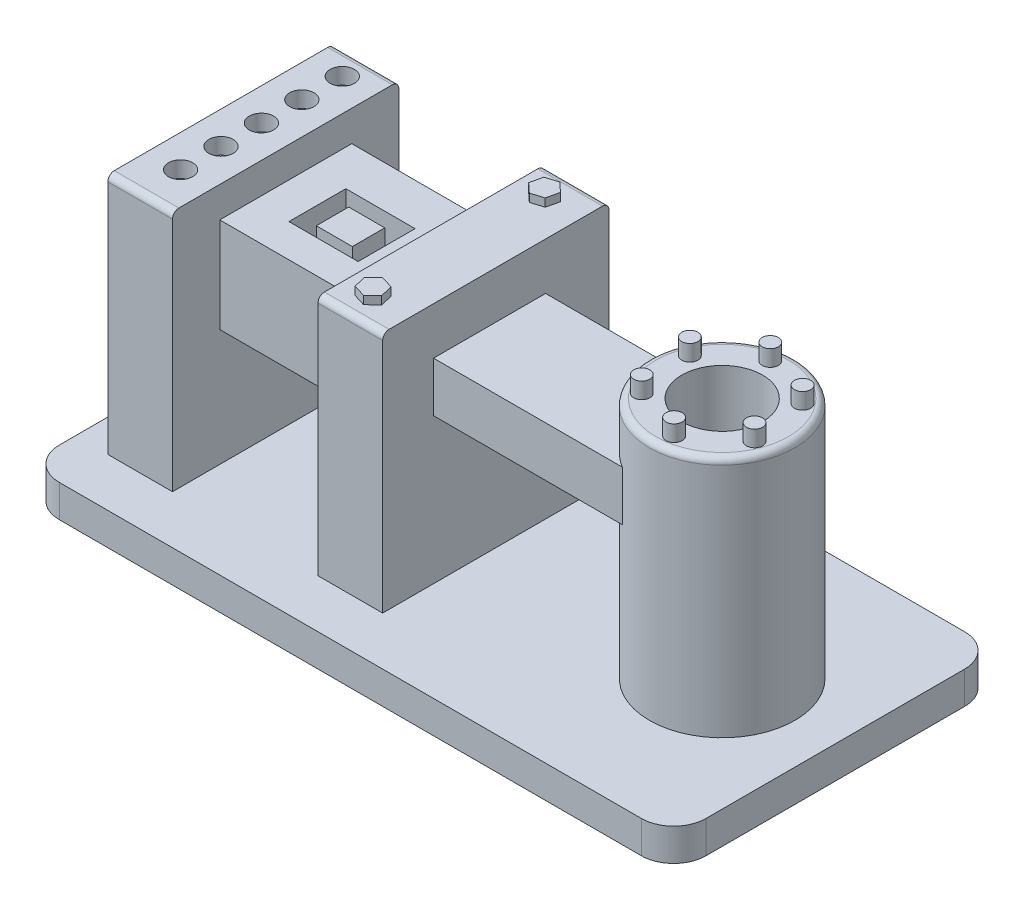
SolidWorks part; units mm, degrees
note: '?' marks a value the reader was unsure of.
ref_plane "Plano frontal" through (0, 0, 0) normal (0, 0, 1) x (1, 0, 0)
ref_plane "Plano superior" through (0, 0, 0) normal (0, 1, 0) x (1, 0, 0)
ref_plane "Plano direito" through (0, 0, 0) normal (1, 0, 0) x (0, 0, -1)
sketch "Esboço2" plane through (0, 0, 0) normal (0, 1, 0) x (1, 0, 0)
  line L1 (200, 100) -> (-200, 100)
  line L2 (200, 100) -> (200, -100)
  line L3 (200, -100) -> (-200, -100)
  line L4 (-200, 100) -> (-200, -100)
  line L5 (200, 100) -> (-200, -100) construction
  line L6 (200, -100) -> (-200, 100) construction
  point P0 (0, 0)
  dimension "D1" = 200
  dimension "D2" = 400
extrude "Ressalto-extrusão1" add sketch "Esboço2" along normal blind 20 contours L2 L1 L4 L3
fillet "Filete4" radius 20 4 edges at (-200, 10, -100) (200, 10, -100) (200, 10, 100) (-200, 10, 100)
sketch "Esboço4" plane through (0, 20, 0) normal (0, 1, 0) x (1, 0, 0)
  line L0 (180, 100) -> (-180, 100) construction
  line L1 (-180, 70) -> (-140, 70)
  line L2 (-180, 70) -> (-180, -70)
  line L3 (-180, -70) -> (-140, -70)
  line L4 (-140, 70) -> (-140, -70)
  line L9 (-50, 70) -> (-10, 70)
  line L10 (-50, 70) -> (-50, -70)
  line L11 (-50, -70) -> (-10, -70)
  line L12 (-10, 70) -> (-10, -70)
  line L13 (-200, 80) -> (-200, -80) construction
  line L14 (180, -100) -> (-180, -100) construction
  circle A0 centre (130, 0) radius 45
  dimension "D9" = 90
  dimension "D1" = 30
  dimension "D2" = 20
  dimension "D3" = 40
  dimension "D4" = 30
  dimension "D5" = 40
  dimension "D6" = 90
  dimension "D7" = 140
  dimension "D8" = 100
extrude "Ressalto-extrusão4" add sketch "Esboço4" along normal blind 150
sketch "Esboço5" plane through (-140, 0, 0) normal (1, 0, 0) x (0, 0, -1)
  line L1 (-40.763, 150.9995) -> (40.8958, 150.9995)
  line L2 (-40.763, 150.9995) -> (-40.763, 92.2832)
  line L3 (-40.763, 92.2832) -> (40.8958, 92.2832)
  line L4 (40.8958, 150.9995) -> (40.8958, 92.2832)
extrude "Ressalto-extrusão5" add sketch "Esboço5" along normal up to surface (90 mm away) separate body up to face at (-50, 95, 0)
sketch "Esboço6" plane through (-10, 0, 0) normal (1, 0, 0) x (0, 0, -1)
  line L1 (-38.5251, 140.8198) -> (30.7711, 140.8198)
  line L2 (-38.5251, 140.8198) -> (-38.5251, 109.9679)
  line L3 (-38.5251, 109.9679) -> (30.7711, 109.9679)
  line L4 (30.7711, 140.8198) -> (30.7711, 109.9679)
extrude "Ressalto-extrusão6" add sketch "Esboço6" along normal up to surface (107.165 mm away)
sketch "Esboço7" plane through (0, 170, 0) normal (0, 1, 0) x (1, 0, 0)
  line L0 (-140, -70) -> (-140, 70) construction
  line L1 (-140, 70) -> (-180, 70) construction
  circle A0 centre (-160, 55) radius 7.5
  dimension "D1" = 15
  dimension "D2" = 20
  dimension "D3" = 15
sketch "Esboço8" plane through (0, 170, 0) normal (0, 1, 0) x (1, 0, 0)
  circle A0 centre (124.7329, 35) radius 5
  arc A1 (97.165, 30.7711) -> (106.7446, -38.5251) centre (130, 0) ccw construction
  dimension "D1" = 10
  dimension "D2" = 35
extrude "Ressalto-extrusão8" add sketch "Esboço8" along normal blind 10
ref_axis "Eixo1" through (130, 170, 0) along (0, -1, 0)?
pattern_circular "PadrãoCircular2" count 6 over 360 about axis through (130, 0, 0) along (0, 1, 0) of "Ressalto-extrusão8"
fillet "Filete6" radius 4 5 edges at (130, 170, 45) (-30, 170, 70) (-30, 170, -70) (-160, 170, -70) (-160, 170, 70)
sketch "Esboço9" plane through (0, 170, 0) normal (0, 1, 0) x (1, 0, 0)
  line L7 (-27.108, 47.6635) -> (-25.3594, 55.3444)
  line L8 (-25.3594, 55.3444) -> (-31.137, 60.6992)
  line L9 (-31.137, 60.6992) -> (-38.6632, 58.3731)
  line L10 (-38.6632, 58.3731) -> (-40.4118, 50.6922)
  line L11 (-40.4118, 50.6922) -> (-34.6342, 45.3374)
  line L12 (-34.6342, 45.3374) -> (-27.108, 47.6635)
  circle A0 centre (-32.8856, 53.0183) radius 6.8221 construction
extrude "Ressalto-extrusão9" add sketch "Esboço9" along normal blind 5
ref_plane "Plano1" through (0, 0, 0) normal (0, 0, -1) x (-1, 0, 0)
mirror "Espelhar1" about plane through (0, 0, 0) normal (0, 0, -1) of "Ressalto-extrusão9"
sketch "Esboço12" plane through (0, 170, 0) normal (0, 1, 0) x (1, 0, 0)
  circle A0 centre (130, 0) radius 25
  dimension "D1" = 50
extrude "Corte-extrusão1" cut sketch "Esboço12" against normal blind 90 contours A0
sketch "Esboço13" plane through (0, 150.9995, 0) normal (0, 1, 0) x (1, 0, 0)
  line L1 (-117.7024, 14.9357) -> (-74.9015, 14.9357)
  line L2 (-117.7024, 14.9357) -> (-117.7024, -20.2858)
  line L3 (-117.7024, -20.2858) -> (-74.9015, -20.2858)
  line L4 (-74.9015, 14.9357) -> (-74.9015, -20.2858)
  line L5 (-107.0022, 6.0189) -> (-84.7101, 6.0189)
  line L6 (-107.0022, 6.0189) -> (-107.0022, -14.044)
  line L7 (-107.0022, -14.044) -> (-84.7101, -14.044)
  line L8 (-84.7101, 6.0189) -> (-84.7101, -14.044)
extrude "Corte-extrusão2" cut sketch "Esboço13" against normal blind 41
extrude "Corte-extrusão3" cut sketch "Esboço7" against normal blind 10 contours A0
pattern_linear "Padrão linear1" count 5 spacing 25 along (0, 0, 1) of "Corte-extrusão3"
